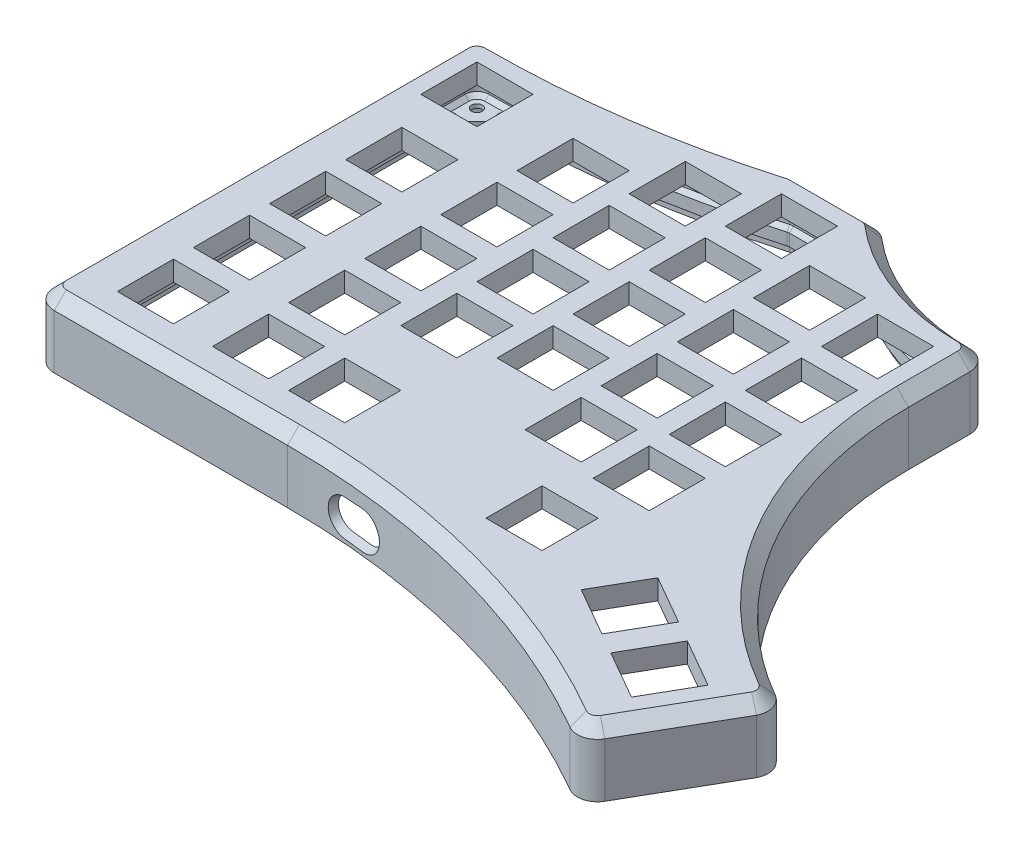
SolidWorks part; units mm, degrees
ref_plane "Front Plane" through (0, 0, 0) normal (0, 0, 1) x (1, 0, 0)
ref_plane "Top Plane" through (0, 0, 0) normal (0, 1, 0) x (1, 0, 0)
ref_plane "Right Plane" through (0, 0, 0) normal (1, 0, 0) x (0, 0, -1)
sketch "Main" plane through (0, 0, 0) normal (0, 1, 0) x (1, 0, 0)
  line L0 (6.4754, 3.5) -> (12.8, 6.5) construction
  line L1 (0, 0) -> (18, 0) construction
  line L2 (0, 0) -> (0, 18) construction
  line L3 (0, 18) -> (18, 18) construction
  line L4 (18, 0) -> (18, 18) construction
  line L5 (2, 16) -> (16, 16)
  line L6 (2, 16) -> (2, 2)
  line L7 (2, 2) -> (16, 2)
  line L8 (16, 16) -> (16, 2)
  line L18 (9, 9) -> (6.4754, 3.5) construction
  line L20 (9, 9) -> (12.8, 6.5) construction
  line L22 (25.4754, 12.5) -> (31.8, 15.5) construction
  line L23 (19, 9) -> (37, 9) construction
  line L24 (19, 9) -> (19, 27) construction
  line L25 (19, 27) -> (37, 27) construction
  line L26 (37, 9) -> (37, 27) construction
  line L27 (21, 25) -> (35, 25)
  line L28 (21, 25) -> (21, 11)
  line L29 (21, 11) -> (35, 11)
  line L30 (35, 25) -> (35, 11)
  line L31 (28, 18) -> (25.4754, 12.5) construction
  line L32 (28, 18) -> (31.8, 15.5) construction
  line L33 (44.4754, 17.5) -> (50.8, 20.5) construction
  line L34 (38, 14) -> (56, 14) construction
  line L35 (38, 14) -> (38, 32) construction
  line L36 (38, 32) -> (56, 32) construction
  line L37 (56, 14) -> (56, 32) construction
  line L38 (40, 30) -> (54, 30)
  line L39 (40, 30) -> (40, 16)
  line L40 (40, 16) -> (54, 16)
  line L41 (54, 30) -> (54, 16)
  line L42 (47, 23) -> (44.4754, 17.5) construction
  line L43 (47, 23) -> (50.8, 20.5) construction
  line L44 (63.4754, 5.5) -> (69.8, 8.5) construction
  line L45 (57, 2) -> (75, 2) construction
  line L46 (57, 2) -> (57, 20) construction
  line L47 (57, 20) -> (75, 20) construction
  line L48 (75, 2) -> (75, 20) construction
  line L49 (59, 18) -> (73, 18)
  line L50 (59, 18) -> (59, 4)
  line L51 (59, 4) -> (73, 4)
  line L52 (73, 18) -> (73, 4)
  line L53 (66, 11) -> (63.4754, 5.5) construction
  line L54 (66, 11) -> (69.8, 8.5) construction
  line L55 (82.4754, 3.5) -> (88.8, 6.5) construction
  line L56 (76, 0) -> (94, 0) construction
  line L57 (76, 0) -> (76, 18) construction
  line L58 (76, 18) -> (94, 18) construction
  line L59 (94, 0) -> (94, 18) construction
  line L60 (78, 16) -> (92, 16)
  line L61 (78, 16) -> (78, 2)
  line L62 (78, 2) -> (92, 2)
  line L63 (92, 16) -> (92, 2)
  line L64 (85, 9) -> (82.4754, 3.5) construction
  line L65 (85, 9) -> (88.8, 6.5) construction
  line L88 (2, -3) -> (16, -3)
  line L89 (2, -3) -> (2, -17)
  line L90 (2, -17) -> (16, -17)
  line L91 (16, -3) -> (16, -17)
  line L92 (21, 6) -> (35, 6)
  line L93 (21, 6) -> (21, -8)
  line L94 (21, -8) -> (35, -8)
  line L95 (35, 6) -> (35, -8)
  line L96 (40, 11) -> (54, 11)
  line L97 (40, 11) -> (40, -3)
  line L98 (40, -3) -> (54, -3)
  line L99 (54, 11) -> (54, -3)
  line L100 (59, -1) -> (73, -1)
  line L101 (59, -1) -> (59, -15)
  line L102 (59, -15) -> (73, -15)
  line L103 (73, -1) -> (73, -15)
  line L104 (78, -3) -> (92, -3)
  line L105 (78, -3) -> (78, -17)
  line L106 (78, -17) -> (92, -17)
  line L107 (92, -3) -> (92, -17)
  line L116 (6.4754, -15.5) -> (12.8, -12.5) construction
  line L117 (0, -19) -> (18, -19) construction
  line L118 (0, -19) -> (0, -1) construction
  line L119 (0, -1) -> (18, -1) construction
  line L120 (18, -19) -> (18, -1) construction
  line L121 (9, -10) -> (6.4754, -15.5) construction
  line L122 (9, -10) -> (12.8, -12.5) construction
  line L123 (25.4754, -6.5) -> (31.8, -3.5) construction
  line L124 (19, -10) -> (37, -10) construction
  line L125 (19, -10) -> (19, 8) construction
  line L126 (19, 8) -> (37, 8) construction
  line L127 (37, -10) -> (37, 8) construction
  line L128 (28, -1) -> (25.4754, -6.5) construction
  line L129 (28, -1) -> (31.8, -3.5) construction
  line L130 (44.4754, -1.5) -> (50.8, 1.5) construction
  line L131 (38, -5) -> (56, -5) construction
  line L132 (38, -5) -> (38, 13) construction
  line L133 (38, 13) -> (56, 13) construction
  line L134 (56, -5) -> (56, 13) construction
  line L135 (47, 4) -> (44.4754, -1.5) construction
  line L136 (47, 4) -> (50.8, 1.5) construction
  line L137 (63.4754, -13.5) -> (69.8, -10.5) construction
  line L138 (57, -17) -> (75, -17) construction
  line L139 (57, -17) -> (57, 1) construction
  line L140 (57, 1) -> (75, 1) construction
  line L141 (75, -17) -> (75, 1) construction
  line L142 (66, -8) -> (63.4754, -13.5) construction
  line L143 (66, -8) -> (69.8, -10.5) construction
  line L144 (82.4754, -15.5) -> (88.8, -12.5) construction
  line L145 (76, -19) -> (94, -19) construction
  line L146 (76, -19) -> (76, -1) construction
  line L147 (76, -1) -> (94, -1) construction
  line L148 (94, -19) -> (94, -1) construction
  line L149 (85, -10) -> (82.4754, -15.5) construction
  line L150 (85, -10) -> (88.8, -12.5) construction
  line L165 (2, -22) -> (16, -22)
  line L166 (2, -22) -> (2, -36)
  line L167 (2, -36) -> (16, -36)
  line L168 (16, -22) -> (16, -36)
  line L169 (21, -13) -> (35, -13)
  line L170 (21, -13) -> (21, -27)
  line L171 (21, -27) -> (35, -27)
  line L172 (35, -13) -> (35, -27)
  line L173 (40, -8) -> (54, -8)
  line L174 (40, -8) -> (40, -22)
  line L175 (40, -22) -> (54, -22)
  line L176 (54, -8) -> (54, -22)
  line L177 (59, -20) -> (73, -20)
  line L178 (59, -20) -> (59, -34)
  line L179 (59, -34) -> (73, -34)
  line L180 (73, -20) -> (73, -34)
  line L181 (78, -22) -> (92, -22)
  line L182 (78, -22) -> (78, -36)
  line L183 (78, -36) -> (92, -36)
  line L184 (92, -22) -> (92, -36)
  line L193 (6.4754, -34.5) -> (12.8, -31.5) construction
  line L194 (0, -38) -> (18, -38) construction
  line L195 (0, -38) -> (0, -20) construction
  line L196 (0, -20) -> (18, -20) construction
  line L197 (18, -38) -> (18, -20) construction
  line L198 (9, -29) -> (6.4754, -34.5) construction
  line L199 (9, -29) -> (12.8, -31.5) construction
  line L200 (25.4754, -25.5) -> (31.8, -22.5) construction
  line L201 (19, -29) -> (37, -29) construction
  line L202 (19, -29) -> (19, -11) construction
  line L203 (19, -11) -> (37, -11) construction
  line L204 (37, -29) -> (37, -11) construction
  line L205 (28, -20) -> (25.4754, -25.5) construction
  line L206 (28, -20) -> (31.8, -22.5) construction
  line L207 (44.4754, -20.5) -> (50.8, -17.5) construction
  line L208 (38, -24) -> (56, -24) construction
  line L209 (38, -24) -> (38, -6) construction
  line L210 (38, -6) -> (56, -6) construction
  line L211 (56, -24) -> (56, -6) construction
  line L212 (47, -15) -> (44.4754, -20.5) construction
  line L213 (47, -15) -> (50.8, -17.5) construction
  line L214 (63.4754, -32.5) -> (69.8, -29.5) construction
  line L215 (57, -36) -> (75, -36) construction
  line L216 (57, -36) -> (57, -18) construction
  line L217 (57, -18) -> (75, -18) construction
  line L218 (75, -36) -> (75, -18) construction
  line L219 (66, -27) -> (63.4754, -32.5) construction
  line L220 (66, -27) -> (69.8, -29.5) construction
  line L221 (82.4754, -34.5) -> (88.8, -31.5) construction
  line L222 (76, -38) -> (94, -38) construction
  line L223 (76, -38) -> (76, -20) construction
  line L224 (76, -20) -> (94, -20) construction
  line L225 (94, -38) -> (94, -20) construction
  line L226 (85, -29) -> (82.4754, -34.5) construction
  line L227 (85, -29) -> (88.8, -31.5) construction
  line L242 (2, -41) -> (16, -41)
  line L243 (2, -41) -> (2, -55)
  line L244 (2, -55) -> (16, -55)
  line L245 (16, -41) -> (16, -55)
  line L246 (21, -32) -> (35, -32)
  line L247 (21, -32) -> (21, -46)
  line L248 (21, -46) -> (35, -46)
  line L249 (35, -32) -> (35, -46)
  line L250 (40, -27) -> (54, -27)
  line L251 (40, -27) -> (40, -41)
  line L252 (40, -41) -> (54, -41)
  line L253 (54, -27) -> (54, -41)
  line L254 (59, -39) -> (73, -39)
  line L255 (59, -39) -> (59, -53)
  line L256 (59, -53) -> (73, -53)
  line L257 (73, -39) -> (73, -53)
  line L258 (78, -41) -> (92, -41)
  line L259 (78, -41) -> (78, -55)
  line L260 (78, -55) -> (92, -55)
  line L261 (92, -41) -> (92, -55)
  line L270 (6.4754, -53.5) -> (12.8, -50.5) construction
  line L271 (0, -57) -> (18, -57) construction
  line L272 (0, -57) -> (0, -39) construction
  line L273 (0, -39) -> (18, -39) construction
  line L274 (18, -57) -> (18, -39) construction
  line L275 (9, -48) -> (6.4754, -53.5) construction
  line L276 (9, -48) -> (12.8, -50.5) construction
  line L277 (25.4754, -44.5) -> (31.8, -41.5) construction
  line L278 (19, -48) -> (37, -48) construction
  line L279 (19, -48) -> (19, -30) construction
  line L280 (19, -30) -> (37, -30) construction
  line L281 (37, -48) -> (37, -30) construction
  line L282 (28, -39) -> (25.4754, -44.5) construction
  line L283 (28, -39) -> (31.8, -41.5) construction
  line L284 (44.4754, -39.5) -> (50.8, -36.5) construction
  line L285 (38, -43) -> (56, -43) construction
  line L286 (38, -43) -> (38, -25) construction
  line L287 (38, -25) -> (56, -25) construction
  line L288 (56, -43) -> (56, -25) construction
  line L289 (47, -34) -> (44.4754, -39.5) construction
  line L290 (47, -34) -> (50.8, -36.5) construction
  line L291 (63.4754, -51.5) -> (69.8, -48.5) construction
  line L292 (57, -55) -> (75, -55) construction
  line L293 (57, -55) -> (57, -37) construction
  line L294 (57, -37) -> (75, -37) construction
  line L295 (75, -55) -> (75, -37) construction
  line L296 (66, -46) -> (63.4754, -51.5) construction
  line L297 (66, -46) -> (69.8, -48.5) construction
  line L298 (82.4754, -53.5) -> (88.8, -50.5) construction
  line L299 (76, -57) -> (94, -57) construction
  line L300 (76, -57) -> (76, -39) construction
  line L301 (76, -39) -> (94, -39) construction
  line L302 (94, -57) -> (94, -39) construction
  line L303 (85, -48) -> (82.4754, -53.5) construction
  line L304 (85, -48) -> (88.8, -50.5) construction
  line L312 (6.4754, -72.5) -> (12.8, -69.5) construction
  line L313 (0, -76) -> (18, -76) construction
  line L314 (0, -76) -> (0, -58) construction
  line L315 (0, -58) -> (18, -58) construction
  line L316 (18, -76) -> (18, -58) construction
  line L317 (2, -60) -> (16, -60)
  line L318 (2, -60) -> (2, -74)
  line L323 (21, -60) -> (35, -60)
  line L324 (21, -60) -> (21, -74)
  line L325 (21, -74) -> (35, -74)
  line L326 (35, -60) -> (35, -74)
  line L327 (25.4754, -72.5) -> (31.8, -69.5) construction
  line L328 (19, -76) -> (37, -76) construction
  line L329 (19, -76) -> (19, -58) construction
  line L330 (-22.0246, 8) -> (-15.7, 11) construction
  line L331 (-28.5, 4.5) -> (-10.5, 4.5) construction
  line L332 (-28.5, 4.5) -> (-28.5, 22.5) construction
  line L333 (-28.5, 22.5) -> (-10.5, 22.5) construction
  line L334 (-10.5, 4.5) -> (-10.5, 22.5) construction
  line L335 (-26.5, 20.5) -> (-12.5, 20.5)
  line L336 (-26.5, 20.5) -> (-26.5, 6.5)
  line L337 (-26.5, 6.5) -> (-12.5, 6.5)
  line L338 (-12.5, 20.5) -> (-12.5, 6.5)
  line L339 (-19.5, 13.5) -> (-22.0246, 8) construction
  line L340 (-19.5, 13.5) -> (-15.7, 11) construction
  line L341 (-21.75, -41) -> (-7.75, -41)
  line L342 (-21.75, -41) -> (-21.75, -55)
  line L343 (-21.75, -55) -> (-7.75, -55)
  line L344 (-7.75, -41) -> (-7.75, -55)
  line L345 (-17.2746, -53.5) -> (-10.95, -50.5) construction
  line L346 (-28.5, -57) -> (-1, -57) construction
  line L347 (-28.5, -57) -> (-28.5, -39) construction
  line L348 (-28.5, -39) -> (-1, -39) construction
  line L349 (-1, -57) -> (-1, -39) construction
  line L350 (-14.75, -48) -> (-17.2746, -53.5) construction
  line L351 (-14.75, -48) -> (-10.95, -50.5) construction
  line L352 (-21.75, -22) -> (-7.75, -22)
  line L353 (-21.75, -22) -> (-21.75, -36)
  line L354 (2, -74) -> (16, -74)
  line L355 (16, -60) -> (16, -74)
  line L356 (9, -67) -> (6.4754, -72.5) construction
  line L357 (9, -67) -> (12.8, -69.5) construction
  line L358 (-17.2746, -72.5) -> (-10.95, -69.5) construction
  line L359 (-28.5, -76) -> (-1, -76) construction
  line L360 (-28.5, -76) -> (-28.5, -58) construction
  line L361 (-28.5, -58) -> (-1, -58) construction
  line L362 (-1, -76) -> (-1, -58) construction
  line L363 (-21.75, -60) -> (-7.75, -60)
  line L364 (-21.75, -60) -> (-21.75, -74)
  line L365 (-21.75, -74) -> (-7.75, -74)
  line L366 (-7.75, -60) -> (-7.75, -74)
  line L367 (-14.75, -67) -> (-17.2746, -72.5) construction
  line L368 (-14.75, -67) -> (-10.95, -69.5) construction
  line L369 (-21.75, -36) -> (-7.75, -36)
  line L370 (-7.75, -22) -> (-7.75, -36)
  line L371 (-17.2746, -34.5) -> (-10.95, -31.5) construction
  line L372 (-28.5, -38) -> (-1, -38) construction
  line L373 (-28.5, -38) -> (-28.5, -20) construction
  line L374 (-28.5, -20) -> (-1, -20) construction
  line L375 (-1, -38) -> (-1, -20) construction
  line L376 (-14.75, -29) -> (-17.2746, -34.5) construction
  line L377 (-14.75, -29) -> (-10.95, -31.5) construction
  line L378 (-21.75, -3) -> (-7.75, -3)
  line L379 (-21.75, -3) -> (-21.75, -17)
  line L380 (-21.75, -17) -> (-7.75, -17)
  line L381 (-7.75, -3) -> (-7.75, -17)
  line L382 (-17.2746, -15.5) -> (-10.95, -12.5) construction
  line L383 (-28.5, -19) -> (-1, -19) construction
  line L384 (-28.5, -19) -> (-28.5, -1) construction
  line L385 (-28.5, -1) -> (-1, -1) construction
  line L386 (-1, -19) -> (-1, -1) construction
  line L387 (-14.75, -10) -> (-17.2746, -15.5) construction
  line L388 (-14.75, -10) -> (-10.95, -12.5) construction
  line L393 (109.2068, -61.578) -> (124.8116, -70.5498) construction
  line L394 (109.2068, -61.578) -> (95.5, -85.4186) construction
  line L398 (124.8116, -70.5498) -> (111.1047, -94.3903) construction
  line L402 (77.7254, -75.5) -> (84.05, -72.5) construction
  line L403 (66.5, -79) -> (94, -79) construction
  line L404 (66.5, -79) -> (66.5, -61) construction
  line L405 (66.5, -61) -> (94, -61) construction
  line L406 (94, -79) -> (94, -61) construction
  line L407 (73.25, -63) -> (87.25, -63)
  line L408 (73.25, -63) -> (73.25, -77)
  line L409 (73.25, -77) -> (87.25, -77)
  line L410 (87.25, -63) -> (87.25, -77)
  line L411 (80.25, -70) -> (77.7254, -75.5) construction
  line L412 (80.25, -70) -> (84.05, -72.5) construction
  line L413 (95.5, -85.4186) -> (111.1047, -94.3903) construction
  line L414 (95.5, -85.4186) -> (124.8116, -70.5498) construction
  line L415 (80.25, -130) -> (110.1558, -77.9842) construction
  line L416 (107.5763, -68.4267) -> (119.7133, -75.4047)
  line L417 (107.5763, -68.4267) -> (100.5983, -80.5637)
  line L418 (119.7133, -75.4047) -> (112.7353, -87.5417)
  line L419 (100.5983, -80.5637) -> (112.7353, -87.5417)
  line L420 (107.5763, -68.4267) -> (112.7353, -87.5417) construction
  line L421 (105.2258, -81.494) -> (110.1558, -77.9842) construction
  line L422 (110.1558, -77.9842) -> (112.204, -82.0455) construction
  line L423 (112.204, -82.0455) -> (105.2258, -81.494) construction
  line L424 (126.5454, -71.5466) -> (142.1502, -80.5184) construction
  line L425 (126.5454, -71.5466) -> (112.8386, -95.3872) construction
  line L426 (142.1502, -80.5184) -> (128.4433, -104.3589) construction
  line L427 (112.8386, -95.3872) -> (128.4433, -104.3589) construction
  line L428 (112.8386, -95.3872) -> (142.1502, -80.5184) construction
  line L430 (124.9149, -78.3953) -> (137.0519, -85.3733)
  line L431 (124.9149, -78.3953) -> (117.9369, -90.5323)
  line L432 (137.0519, -85.3733) -> (130.0739, -97.5103)
  line L433 (117.9369, -90.5323) -> (130.0739, -97.5103)
  line L434 (124.9149, -78.3953) -> (130.0739, -97.5103) construction
  line L435 (122.5644, -91.4626) -> (127.4944, -87.9528) construction
  line L436 (127.4944, -87.9528) -> (129.5426, -92.0141) construction
  line L437 (129.5426, -92.0141) -> (122.5644, -91.4626) construction
  line L448 (19, -58) -> (37, -58) construction
  line L449 (37, -76) -> (37, -58) construction
  line L450 (28, -67) -> (25.4754, -72.5) construction
  line L451 (28, -67) -> (31.8, -69.5) construction
  circle A0 centre (9, 9) radius 2 construction
  circle A1 centre (6.4754, 3.5) radius 1.5 construction
  circle A2 centre (12.8, 6.5) radius 1.5 construction
  circle A6 centre (28, 18) radius 2 construction
  circle A7 centre (25.4754, 12.5) radius 1.5 construction
  circle A8 centre (31.8, 15.5) radius 1.5 construction
  circle A9 centre (47, 23) radius 2 construction
  circle A10 centre (44.4754, 17.5) radius 1.5 construction
  circle A11 centre (50.8, 20.5) radius 1.5 construction
  circle A12 centre (66, 11) radius 2 construction
  circle A13 centre (63.4754, 5.5) radius 1.5 construction
  circle A14 centre (69.8, 8.5) radius 1.5 construction
  circle A15 centre (85, 9) radius 2 construction
  circle A16 centre (82.4754, 3.5) radius 1.5 construction
  circle A17 centre (88.8, 6.5) radius 1.5 construction
  circle A24 centre (9, -10) radius 2 construction
  circle A25 centre (6.4754, -15.5) radius 1.5 construction
  circle A26 centre (12.8, -12.5) radius 1.5 construction
  circle A27 centre (28, -1) radius 2 construction
  circle A28 centre (25.4754, -6.5) radius 1.5 construction
  circle A29 centre (31.8, -3.5) radius 1.5 construction
  circle A30 centre (47, 4) radius 2 construction
  circle A31 centre (44.4754, -1.5) radius 1.5 construction
  circle A32 centre (50.8, 1.5) radius 1.5 construction
  circle A33 centre (66, -8) radius 2 construction
  circle A34 centre (63.4754, -13.5) radius 1.5 construction
  circle A35 centre (69.8, -10.5) radius 1.5 construction
  circle A36 centre (85, -10) radius 2 construction
  circle A37 centre (82.4754, -15.5) radius 1.5 construction
  circle A38 centre (88.8, -12.5) radius 1.5 construction
  circle A45 centre (9, -29) radius 2 construction
  circle A46 centre (6.4754, -34.5) radius 1.5 construction
  circle A47 centre (12.8, -31.5) radius 1.5 construction
  circle A48 centre (28, -20) radius 2 construction
  circle A49 centre (25.4754, -25.5) radius 1.5 construction
  circle A50 centre (31.8, -22.5) radius 1.5 construction
  circle A51 centre (47, -15) radius 2 construction
  circle A52 centre (44.4754, -20.5) radius 1.5 construction
  circle A53 centre (50.8, -17.5) radius 1.5 construction
  circle A54 centre (66, -27) radius 2 construction
  circle A55 centre (63.4754, -32.5) radius 1.5 construction
  circle A56 centre (69.8, -29.5) radius 1.5 construction
  circle A57 centre (85, -29) radius 2 construction
  circle A58 centre (82.4754, -34.5) radius 1.5 construction
  circle A59 centre (88.8, -31.5) radius 1.5 construction
  circle A63 centre (9, -67) radius 2 construction
  circle A64 centre (6.4754, -72.5) radius 1.5 construction
  circle A65 centre (12.8, -69.5) radius 1.5 construction
  circle A66 centre (9, -48) radius 2 construction
  circle A67 centre (6.4754, -53.5) radius 1.5 construction
  circle A68 centre (12.8, -50.5) radius 1.5 construction
  circle A69 centre (28, -39) radius 2 construction
  circle A70 centre (25.4754, -44.5) radius 1.5 construction
  circle A71 centre (31.8, -41.5) radius 1.5 construction
  circle A72 centre (47, -34) radius 2 construction
  circle A73 centre (44.4754, -39.5) radius 1.5 construction
  circle A74 centre (50.8, -36.5) radius 1.5 construction
  circle A75 centre (66, -46) radius 2 construction
  circle A76 centre (63.4754, -51.5) radius 1.5 construction
  circle A77 centre (69.8, -48.5) radius 1.5 construction
  circle A78 centre (85, -48) radius 2 construction
  circle A79 centre (82.4754, -53.5) radius 1.5 construction
  circle A80 centre (88.8, -50.5) radius 1.5 construction
  circle A81 centre (-14.75, -67) radius 2 construction
  circle A82 centre (-17.2746, -72.5) radius 1.5 construction
  circle A83 centre (-10.95, -69.5) radius 1.5 construction
  circle A84 centre (28, -67) radius 2 construction
  circle A85 centre (25.4754, -72.5) radius 1.5 construction
  circle A86 centre (31.8, -69.5) radius 1.5 construction
  circle A87 centre (-19.5, 13.5) radius 2 construction
  circle A88 centre (-22.0246, 8) radius 1.5 construction
  circle A89 centre (-15.7, 11) radius 1.5 construction
  circle A90 centre (-14.75, -48) radius 2 construction
  circle A91 centre (-17.2746, -53.5) radius 1.5 construction
  circle A92 centre (-10.95, -50.5) radius 1.5 construction
  circle A93 centre (-14.75, -29) radius 2 construction
  circle A94 centre (-17.2746, -34.5) radius 1.5 construction
  circle A95 centre (-10.95, -31.5) radius 1.5 construction
  circle A96 centre (-14.75, -10) radius 2 construction
  circle A97 centre (-17.2746, -15.5) radius 1.5 construction
  circle A98 centre (-10.95, -12.5) radius 1.5 construction
  circle A102 centre (80.25, -70) radius 2 construction
  circle A103 centre (77.7254, -75.5) radius 1.5 construction
  circle A104 centre (84.05, -72.5) radius 1.5 construction
  circle A105 centre (80.25, -130) radius 60 construction
  circle A106 centre (110.1558, -77.9842) radius 2 construction
  circle A107 centre (105.2258, -81.494) radius 1.5 construction
  circle A108 centre (112.204, -82.0455) radius 1.5 construction
  circle A109 centre (127.4944, -87.9528) radius 2 construction
  circle A110 centre (122.5644, -91.4626) radius 1.5 construction
  circle A111 centre (129.5426, -92.0141) radius 1.5 construction
  circle A112 centre (62, -66) radius 1.5 construction
  point P9 (9, 16)
  point P10 (9, 18)
  point P11 (2, 9)
  point P12 (0, 9)
  point P30 (28, 25)
  point P31 (28, 27)
  point P32 (21, 18)
  point P33 (19, 18)
  point P46 (47, 30)
  point P47 (47, 32)
  point P48 (40, 23)
  point P49 (38, 23)
  point P64 (66, 18)
  point P65 (66, 20)
  point P66 (59, 11)
  point P67 (57, 11)
  point P82 (85, 16)
  point P83 (85, 18)
  point P84 (78, 9)
  point P85 (76, 9)
  point P102 (9, -60)
  point P103 (9, -58)
  point P104 (2, -67)
  point P105 (0, -67)
  point P124 (-14.75, -60)
  point P125 (-14.75, -58)
  point P126 (-21.75, -67)
  point P127 (-28.5, -67)
  point P297 (-19.5, 20.5)
  point P298 (-19.5, 22.5)
  point P299 (-26.5, 13.5)
  point P300 (-28.5, 13.5)
  point P423 (103.3024, -89.9045)
  point P444 (80.25, -63)
  point P445 (80.25, -61)
  point P446 (73.25, -70)
  point P447 (66.5, -70)
  dimension "D6" = 4
  dimension "D7" = 3
  dimension "D10" = 1
  dimension "D11" = 12
  dimension "D21" = 9.5
  dimension "D22" = 1.5
  dimension "D26" = 120
  dimension "D28" = 3
  dimension "D1" = 18
  dimension "D2" = 14
  dimension "D3" = 3.2
  dimension "D4" = 4.5
  dimension "D5" = 7
  dimension "D8" = 1
  dimension "D9" = 5
  dimension "D12" = 1
  dimension "D13" = 9
  dimension "D14" = 1
  dimension "D15" = 2
  dimension "D16" = 2
  dimension "D17" = 27.5
  dimension "D18" = 1
  dimension "D20" = 1
  dimension "D24" = 1
  dimension "D25" = 8
  dimension "D27" = 2
  dimension "D29" = 15
  dimension "D30" = 32
  dimension "D19" = 4
  dimension "D23" = 4
sketch "Sketch1" plane through (0, 0, 0) normal (0, 1, 0) x (1, 0, 0)
  line L0 (-33.5, 22.5) -> (-33.5, -78)
  line L1 (-28.5, -83) -> (29.7127, -83)
  line L2 (132.778, -106.8511) -> (146.594, -82.8206)
  line L3 (99, 2.7142) -> (99, 18)
  line L6 (38, 32) -> (56, 32) construction
  line L7 (-28.5, -76) -> (-28.5, -58) construction
  line L8 (144.6447, -76.1796) -> (94, -47.0621) construction
  line L9 (142.1502, -80.5184) -> (128.4433, -104.3589) construction
  line L10 (94, 0) -> (94, 18) construction
  line L11 (94, -57) -> (94, -39) construction
  line L12 (128.4433, -104.3589) -> (125.9512, -108.6936) construction
  line L13 (109.2068, -61.578) -> (124.8116, -70.5498) construction
  line L14 (125.9512, -108.6936) -> (74.3045, -79) construction
  line L15 (66.5, -79) -> (94, -79) construction
  line L17 (95.5, -85.4186) -> (111.1047, -94.3903) construction
  line L20 (94, 23) -> (56, 23) construction
  line L21 (56, 14) -> (56, 32) construction
  line L23 (38, 37) -> (56, 37)
  line L27 (38, 14) -> (38, 32) construction
  line L28 (-28.5, 4.5) -> (-28.5, 22.5) construction
  line L29 (-31.5, 22.5) -> (-31.5, -78) construction
  line L30 (-28.5, -81) -> (29.7127, -81) construction
  line L31 (131.0441, -105.8542) -> (144.8356, -81.8665) construction
  line L32 (97, 2.7142) -> (97, 18) construction
  line L33 (38, 35) -> (56, 35) construction
  line L39 (107.5763, -68.4267) -> (119.7133, -75.4047)
  line L40 (-26.5, 20.5) -> (-12.5, 20.5)
  line L41 (-26.5, 20.5) -> (-26.5, 6.5)
  line L42 (-26.5, 6.5) -> (-12.5, 6.5)
  line L43 (-12.5, 20.5) -> (-12.5, 6.5)
  line L44 (-21.75, -3) -> (-7.75, -3)
  line L45 (-21.75, -3) -> (-21.75, -17)
  line L46 (-21.75, -17) -> (-7.75, -17)
  line L47 (-7.75, -3) -> (-7.75, -17)
  line L48 (-21.75, -22) -> (-7.75, -22)
  line L49 (-21.75, -22) -> (-21.75, -36)
  line L50 (-21.75, -36) -> (-7.75, -36)
  line L51 (-7.75, -22) -> (-7.75, -36)
  line L52 (-21.75, -41) -> (-7.75, -41)
  line L53 (-21.75, -41) -> (-21.75, -55)
  line L54 (-21.75, -55) -> (-7.75, -55)
  line L55 (-7.75, -41) -> (-7.75, -55)
  line L56 (-21.75, -60) -> (-7.75, -60)
  line L57 (-21.75, -60) -> (-21.75, -74)
  line L58 (-21.75, -74) -> (-7.75, -74)
  line L59 (-7.75, -60) -> (-7.75, -74)
  line L60 (2, 16) -> (16, 16)
  line L61 (2, 16) -> (2, 2)
  line L62 (2, 2) -> (16, 2)
  line L63 (16, 16) -> (16, 2)
  line L64 (2, -3) -> (16, -3)
  line L65 (2, -3) -> (2, -17)
  line L66 (2, -17) -> (16, -17)
  line L67 (16, -3) -> (16, -17)
  line L68 (2, -22) -> (16, -22)
  line L69 (2, -22) -> (2, -36)
  line L70 (2, -36) -> (16, -36)
  line L71 (16, -22) -> (16, -36)
  line L72 (2, -41) -> (16, -41)
  line L73 (2, -41) -> (2, -55)
  line L74 (2, -55) -> (16, -55)
  line L75 (16, -41) -> (16, -55)
  line L76 (2, -60) -> (16, -60)
  line L77 (2, -60) -> (2, -74)
  line L78 (2, -74) -> (16, -74)
  line L79 (16, -60) -> (16, -74)
  line L80 (21, -60) -> (35, -60)
  line L81 (21, -60) -> (21, -74)
  line L82 (21, -74) -> (35, -74)
  line L83 (35, -60) -> (35, -74)
  line L84 (21, -32) -> (35, -32)
  line L85 (21, -32) -> (21, -46)
  line L86 (21, -46) -> (35, -46)
  line L87 (35, -32) -> (35, -46)
  line L88 (21, 25) -> (35, 25)
  line L89 (21, 25) -> (21, 11)
  line L90 (21, 11) -> (35, 11)
  line L91 (35, 25) -> (35, 11)
  line L92 (21, 6) -> (35, 6)
  line L93 (21, 6) -> (21, -8)
  line L94 (21, -8) -> (35, -8)
  line L95 (35, 6) -> (35, -8)
  line L96 (21, -13) -> (35, -13)
  line L97 (21, -13) -> (21, -27)
  line L98 (21, -27) -> (35, -27)
  line L99 (35, -13) -> (35, -27)
  line L100 (40, 30) -> (54, 30)
  line L101 (40, 30) -> (40, 16)
  line L102 (40, 16) -> (54, 16)
  line L103 (54, 30) -> (54, 16)
  line L104 (40, 11) -> (54, 11)
  line L105 (40, 11) -> (40, -3)
  line L106 (40, -3) -> (54, -3)
  line L107 (54, 11) -> (54, -3)
  line L108 (40, -8) -> (54, -8)
  line L109 (40, -8) -> (40, -22)
  line L110 (40, -22) -> (54, -22)
  line L111 (54, -8) -> (54, -22)
  line L112 (40, -27) -> (54, -27)
  line L113 (40, -27) -> (40, -41)
  line L114 (40, -41) -> (54, -41)
  line L115 (54, -27) -> (54, -41)
  line L116 (59, 18) -> (73, 18)
  line L117 (59, 18) -> (59, 4)
  line L118 (59, 4) -> (73, 4)
  line L119 (73, 18) -> (73, 4)
  line L120 (78, 16) -> (92, 16)
  line L121 (78, 16) -> (78, 2)
  line L122 (78, 2) -> (92, 2)
  line L123 (92, 16) -> (92, 2)
  line L124 (59, -1) -> (73, -1)
  line L125 (59, -1) -> (59, -15)
  line L126 (59, -15) -> (73, -15)
  line L127 (73, -1) -> (73, -15)
  line L128 (78, -3) -> (92, -3)
  line L129 (78, -3) -> (78, -17)
  line L130 (78, -17) -> (92, -17)
  line L131 (92, -3) -> (92, -17)
  line L132 (59, -20) -> (73, -20)
  line L133 (59, -20) -> (59, -34)
  line L134 (59, -34) -> (73, -34)
  line L135 (73, -20) -> (73, -34)
  line L136 (78, -22) -> (92, -22)
  line L137 (78, -22) -> (78, -36)
  line L138 (78, -36) -> (92, -36)
  line L139 (92, -22) -> (92, -36)
  line L140 (59, -39) -> (73, -39)
  line L141 (59, -39) -> (59, -53)
  line L142 (59, -53) -> (73, -53)
  line L143 (73, -39) -> (73, -53)
  line L144 (78, -41) -> (92, -41)
  line L145 (78, -41) -> (78, -55)
  line L146 (78, -55) -> (92, -55)
  line L147 (92, -41) -> (92, -55)
  line L148 (73.25, -63) -> (87.25, -63)
  line L149 (73.25, -63) -> (73.25, -77)
  line L150 (73.25, -77) -> (87.25, -77)
  line L151 (87.25, -63) -> (87.25, -77)
  line L152 (107.5763, -68.4267) -> (100.5983, -80.5637)
  line L153 (119.7133, -75.4047) -> (112.7353, -87.5417)
  line L154 (100.5983, -80.5637) -> (112.7353, -87.5417)
  line L155 (124.9149, -78.3953) -> (137.0519, -85.3733)
  line L156 (124.9149, -78.3953) -> (117.9369, -90.5323)
  line L157 (137.0519, -85.3733) -> (130.0739, -97.5103)
  line L158 (117.9369, -90.5323) -> (130.0739, -97.5103)
  arc A0 (29.7127, -83) -> (125.9512, -108.6936) centre (29.7127, -276.0835) cw
  arc A4 (94, 23) -> (59.2439, 35.8049) centre (94, 76.5714) cw
  arc A7 (36.6, 36.8) -> (-28.5, 27.5) centre (-28.5, 260) cw
  arc A10 (125.9512, -108.6936) -> (132.778, -106.8511) centre (128.4433, -104.3589) ccw
  arc A11 (-33.5, -78) -> (-28.5, -83) centre (-28.5, -78) ccw
  arc A14 (146.594, -82.8206) -> (144.6447, -76.1796) centre (142.1502, -80.5184) ccw
  arc A15 (144.6447, -76.1796) -> (99, 2.7142) centre (190.0036, 2.7142) cw
  arc A16 (99, 18) -> (94, 23) centre (94, 18) ccw
  arc A17 (-33.5, 22.5) -> (-28.5, 27.5) centre (-28.5, 22.5) cw
  arc A29 (36.6, 36.8) -> (38, 37) centre (38, 32) cw
  arc A30 (56, 37) -> (59.2439, 35.8049) centre (56, 32) cw
  arc A31 (37.16, 34.88) -> (-28.5, 25.5) centre (-28.5, 260) cw construction
  arc A32 (-31.5, 22.5) -> (-28.5, 25.5) centre (-28.5, 22.5) cw construction
  arc A33 (-31.5, -78) -> (-28.5, -81) centre (-28.5, -78) ccw construction
  arc A34 (29.7127, -81) -> (126.9481, -106.9597) centre (29.7127, -276.0835) cw construction
  arc A35 (126.9481, -106.9597) -> (131.0441, -105.8542) centre (128.4433, -104.3589) ccw construction
  arc A36 (144.8356, -81.8665) -> (143.6478, -77.9134) centre (142.1502, -80.5184) ccw construction
  arc A37 (143.6478, -77.9134) -> (97, 2.7142) centre (190.0036, 2.7142) cw construction
  arc A38 (97, 18) -> (94, 21) centre (94, 18) ccw construction
  arc A39 (94, 21) -> (57.9463, 34.2829) centre (94, 76.5714) cw construction
  arc A40 (56, 35) -> (57.9463, 34.2829) centre (56, 32) cw construction
  arc A41 (37.16, 34.88) -> (38, 35) centre (38, 32) cw construction
  dimension "D1" = 4
  dimension "D2" = 5
  dimension "D7" = 5.0048
  dimension "D8" = 5
  dimension "D3" = 5
  dimension "D4" = 5
  dimension "D5" = 5
  dimension "D6" = 5
  dimension "D9" = 2
extrude "Main_plate" add sketch "Sketch1" against normal blind 5
chamfer "Main_plate_chamfer" distance 3 16 edges at (146.9524, 0, 79.1088) (111.2334, 0, 42.859) (99, 0, -10.3571) (97.5355, 0, -21.5355) (75.4801, 0, -26.303) (4.3805, 0, -29.8367) (-32.0355, 0, -26.0355) (139.686, 0, 94.8358) (-33.5, 0, 27.75) (129.7462, 0, 109.1862) (-32.0355, 0, 81.5355) (79.5173, 0, 89.534) (0.6063, 0, 83) (57.7285, 0, -36.6917) (47, 0, -37) (37.2929, 0, -36.9497)
sketch "Sketch3" plane through (0, -5, 0) normal (0, -1, 0) x (1, 0, 0)
  line L0 (-28.5, 83) -> (29.7127, 83)
  line L1 (132.778, 106.8511) -> (146.594, 82.8206)
  line L2 (-33.5, 78) -> (-33.5, -22.5)
  line L3 (99, -18) -> (99, -2.7142)
  line L8 (38, -37) -> (56, -37)
  line L9 (-28.5, 81) -> (29.7127, 81)
  line L10 (131.0441, 105.8542) -> (144.8356, 81.8665)
  line L11 (97, -18) -> (97, -2.7142)
  line L12 (38, -35) -> (56, -35)
  line L13 (-31.5, 78) -> (-31.5, -22.5)
  arc A0 (29.7127, 83) -> (125.9512, 108.6936) centre (29.7127, 276.0835) ccw
  arc A1 (125.9512, 108.6936) -> (132.778, 106.8511) centre (128.4433, 104.3589) cw
  arc A2 (-28.5, 83) -> (-33.5, 78) centre (-28.5, 78) ccw
  arc A3 (-33.5, -22.5) -> (-28.5, -27.5) centre (-28.5, -22.5) ccw
  arc A8 (94, -23) -> (99, -18) centre (94, -18) ccw
  arc A10 (144.6447, 76.1796) -> (146.594, 82.8206) centre (142.1502, 80.5184) ccw
  arc A11 (144.6447, 76.1796) -> (99, -2.7142) centre (190.0036, -2.7142) ccw
  arc A23 (94, -23) -> (99, -18) centre (94, -18) ccw construction
  arc A24 (-28.5, -27.5) -> (36.6, -36.8) centre (-28.5, -260) cw
  arc A25 (36.6, -36.8) -> (38, -37) centre (38, -32) ccw
  arc A26 (94, -23) -> (59.2439, -35.8049) centre (94, -76.5714) ccw
  arc A27 (59.2439, -35.8049) -> (56, -37) centre (56, -32) cw
  arc A28 (29.7127, 81) -> (126.9481, 106.9597) centre (29.7127, 276.0835) ccw
  arc A29 (126.9481, 106.9597) -> (131.0441, 105.8542) centre (128.4433, 104.3589) cw
  arc A30 (143.6478, 77.9134) -> (144.8356, 81.8665) centre (142.1502, 80.5184) ccw
  arc A31 (143.6478, 77.9134) -> (97, -2.7142) centre (190.0036, -2.7142) ccw
  arc A32 (94, -21) -> (97, -18) centre (94, -18) ccw
  arc A33 (94, -21) -> (57.9463, -34.2829) centre (94, -76.5714) ccw
  arc A34 (57.9463, -34.2829) -> (56, -35) centre (56, -32) cw
  arc A35 (37.16, -34.88) -> (38, -35) centre (38, -32) ccw
  arc A36 (-28.5, -25.5) -> (37.16, -34.88) centre (-28.5, -260) cw
  arc A37 (-31.5, -22.5) -> (-28.5, -25.5) centre (-28.5, -22.5) ccw
  arc A38 (-28.5, 81) -> (-31.5, 78) centre (-28.5, 78) ccw
  dimension "D1" = 2
extrude "Wall" add sketch "Sketch3" along normal blind 11.5
sketch "Sketch4" plane through (0, -5, 0) normal (0, -1, 0) x (1, 0, 0)
  line L0 (54.62, 75.25) -> (54.62, 44.77) construction
  line L2 (56.12, 75.25) -> (56.12, 44.77)
  line L12 (53.12, 75.25) -> (53.12, 44.77)
  line L16 (39.38, 44.77) -> (39.38, 75.25) construction
  line L17 (37.88, 44.77) -> (37.88, 75.25)
  line L18 (40.88, 44.77) -> (40.88, 75.25)
  arc A9 (56.12, 75.25) -> (53.12, 75.25) centre (54.62, 75.25) ccw
  arc A10 (53.12, 44.77) -> (56.12, 44.77) centre (54.62, 44.77) ccw
  arc A11 (37.88, 44.77) -> (40.88, 44.77) centre (39.38, 44.77) ccw
  arc A12 (40.88, 75.25) -> (37.88, 75.25) centre (39.38, 75.25) ccw
  point P2 (54.62, 60.01)
  point P7 (39.38, 60.01)
  dimension "D1" = 3
extrude "Nice-nano_extrude" cut sketch "Sketch4" against normal blind 2
ref_plane "Plane1" through (0, -14.5, 0) normal (0, -1, 0) x (-1, 0, 0)
sketch "Sketch8" plane through (0, -14.5, 0) normal (0, -1, 0) x (-1, 0, 0)
  line L0 (-39.38, -80.2385) -> (-39.38, -81.2397)
  line L2 (-54.62, -81.5883) -> (-54.62, -82.5966)
  line L51 (-29.7127, -80) -> (28.5, -80)
  line L52 (30.5, -78) -> (30.5, 22.5)
  line L53 (-38, 34) -> (-56, 34)
  line L54 (-96, 18) -> (-96, 2.7142)
  line L55 (-143.9531, -81.395) -> (-130.1772, -105.3558)
  line L56 (-144.8356, -81.8665) -> (-131.0441, -105.8542)
  line L57 (-97, 18) -> (-97, 2.7142)
  line L58 (-38, 35) -> (-56, 35)
  line L59 (31.5, -78) -> (31.5, 22.5)
  line L60 (-29.7127, -81) -> (28.5, -81)
  line L61 (-144.8356, -81.8665) -> (-131.0441, -105.8542)
  line L62 (-97, 18) -> (-97, 2.7142)
  line L63 (-38, 35) -> (-56, 35)
  line L64 (31.5, -78) -> (31.5, 22.5)
  line L65 (-29.7127, -81) -> (28.5, -81)
  arc A0 (-54.62, -81.5883) -> (-127.4465, -106.0928) centre (-29.7127, -276.0835) ccw
  arc A1 (-29.7127, -80) -> (-127.4465, -106.0928) centre (-29.7127, -276.0835) ccw construction
  arc A2 (-54.62, -82.5966) -> (-126.9481, -106.9597) centre (-29.7127, -276.0835) ccw
  arc A3 (-29.7127, -81) -> (-126.9481, -106.9597) centre (-29.7127, -276.0835) ccw construction
  arc A4 (-40.88, -75.25) -> (-37.88, -75.25) centre (-39.38, -75.25) ccw construction
  arc A5 (-56.12, -75.25) -> (-53.12, -75.25) centre (-54.62, -75.25) ccw construction
  arc A91 (28.5, -80) -> (30.5, -78) centre (28.5, -78) ccw
  arc A92 (30.5, 22.5) -> (28.5, 24.5) centre (28.5, 22.5) ccw
  arc A93 (-37.44, 33.92) -> (28.5, 24.5) centre (28.5, 260) ccw
  arc A94 (-37.44, 33.92) -> (-38, 34) centre (-38, 32) ccw
  arc A95 (-56, 34) -> (-57.2976, 33.522) centre (-56, 32) ccw
  arc A96 (-94, 20) -> (-57.2976, 33.522) centre (-94, 76.5714) ccw
  arc A97 (-94, 20) -> (-96, 18) centre (-94, 18) ccw
  arc A98 (-143.1494, -78.7803) -> (-96, 2.7142) centre (-190.0036, 2.7142) ccw
  arc A99 (-143.1494, -78.7803) -> (-143.9531, -81.395) centre (-142.1502, -80.5184) ccw
  arc A100 (-130.1772, -105.3558) -> (-127.4465, -106.0928) centre (-128.4433, -104.3589) ccw
  arc A101 (-29.7127, -80) -> (-39.38, -80.2385) centre (-29.7127, -276.0835) ccw
  arc A102 (-29.7127, -81) -> (-126.9481, -106.9597) centre (-29.7127, -276.0835) ccw
  arc A103 (-131.0441, -105.8542) -> (-126.9481, -106.9597) centre (-128.4433, -104.3589) ccw
  arc A104 (-143.6478, -77.9134) -> (-144.8356, -81.8665) centre (-142.1502, -80.5184) ccw
  arc A105 (-143.6478, -77.9134) -> (-97, 2.7142) centre (-190.0036, 2.7142) ccw
  arc A106 (-94, 21) -> (-97, 18) centre (-94, 18) ccw
  arc A107 (-94, 21) -> (-57.9463, 34.2829) centre (-94, 76.5714) ccw
  arc A108 (-56, 35) -> (-57.9463, 34.2829) centre (-56, 32) ccw
  arc A109 (-37.16, 34.88) -> (-38, 35) centre (-38, 32) ccw
  arc A110 (-37.16, 34.88) -> (28.5, 25.5) centre (28.5, 260) ccw
  arc A111 (31.5, 22.5) -> (28.5, 25.5) centre (28.5, 22.5) ccw
  arc A112 (28.5, -81) -> (31.5, -78) centre (28.5, -78) ccw
  arc A113 (-29.7127, -81) -> (-39.38, -81.2397) centre (-29.7127, -276.0835) ccw
  arc A114 (-131.0441, -105.8542) -> (-126.9481, -106.9597) centre (-128.4433, -104.3589) ccw
  arc A115 (-143.6478, -77.9134) -> (-144.8356, -81.8665) centre (-142.1502, -80.5184) ccw
  arc A116 (-143.6478, -77.9134) -> (-97, 2.7142) centre (-190.0036, 2.7142) ccw
  arc A117 (-94, 21) -> (-97, 18) centre (-94, 18) ccw
  arc A118 (-94, 21) -> (-57.9463, 34.2829) centre (-94, 76.5714) ccw
  arc A119 (-56, 35) -> (-57.9463, 34.2829) centre (-56, 32) ccw
  arc A120 (-37.16, 34.88) -> (-38, 35) centre (-38, 32) ccw
  arc A121 (-37.16, 34.88) -> (28.5, 25.5) centre (28.5, 260) ccw
  arc A122 (31.5, 22.5) -> (28.5, 25.5) centre (28.5, 22.5) ccw
  arc A123 (28.5, -81) -> (31.5, -78) centre (28.5, -78) ccw
  point P29 (-54.62, -76.75)
  point P35 (-39.38, -76.75)
  dimension "D1" = 0
  dimension "D2" = 1
extrude "Side" add sketch "Sketch8" against normal blind 3
chamfer "Side_chamfer" distance 1 angle 45 17 edges at (137.9398, -11.5, 93.8604) (129.2251, -11.5, 107.2553) (34.5478, -11.5, 81.0599) (0.6063, -11.5, 81) (-30.6213, -11.5, 80.1213) (-31.5, -11.5, 27.75) (-30.6213, -11.5, -24.6213) (145.0279, -11.5, 79.6537) (37.5757, -11.5, -34.9698) (109.5023, -11.5, 43.8606) (47, -11.5, -35) (97, -11.5, -10.3571) (57.0371, -11.5, -34.815) (96.1213, -11.5, -20.1213) (74.7887, -11.5, -24.4264) (91.9871, -11.5, 91.2066) (4.6633, -11.5, -27.8568)
sketch "Sketch18" plane through (0, -14.5, 0) normal (0, -1, 0) x (1, 0, 0)
  line L15 (29.7127, 81) -> (-28.5, 81) construction
  line L16 (-31.5, 78) -> (-31.5, -22.5) construction
  line L17 (-26.5, -20.5) -> (-26.5, -6.5) construction
  line L18 (-23.427, 76.2747) -> (-24.6932, 81)
  line L21 (144.8356, 81.8665) -> (131.0441, 105.8542) construction
  line L22 (97, -18) -> (97, -2.7142) construction
  line L23 (-31.5, 78) -> (-31.5, -22.5) construction
  line L27 (-23.427, 76.2747) -> (-24.6524, 80.8476) construction
  line L28 (-25.8771, 79.6229) -> (-28.777, 80.3999) construction
  line L29 (-28.777, 80.3999) -> (-30.8999, 78.277) construction
  line L30 (-30.8999, 78.277) -> (-30.1229, 75.3771) construction
  line L31 (-30.1229, 75.3771) -> (-27.223, 74.6001) construction
  line L32 (-27.223, 74.6001) -> (-25.1001, 76.723) construction
  line L33 (-25.1001, 76.723) -> (-25.8771, 79.6229) construction
  line L34 (-24.6524, 80.8476) -> (-29.2253, 82.073) construction
  line L35 (-29.2253, 82.073) -> (-32.573, 78.7253) construction
  line L36 (-32.573, 78.7253) -> (-31.3476, 74.1524) construction
  line L37 (-31.3476, 74.1524) -> (-26.7747, 72.927) construction
  line L38 (-26.7747, 72.927) -> (-23.427, 76.2747)
  line L39 (-26.7747, 72.927) -> (-31.5, 74.1932)
  line L41 (-31.5, 74.1932) -> (-31.5, 81)
  line L42 (-31.5, 81) -> (-24.6932, 81)
  line L43 (-25.8771, -24.1234) -> (-25.1001, -21.2235) construction
  line L44 (-25.1001, -21.2235) -> (-27.223, -19.1006) construction
  line L45 (-27.223, -19.1006) -> (-30.1229, -19.8776) construction
  line L46 (-30.1229, -19.8776) -> (-30.8999, -22.7776) construction
  line L47 (-30.8999, -22.7776) -> (-28.777, -24.9004) construction
  line L48 (-28.777, -24.9004) -> (-25.8771, -24.1234) construction
  line L49 (-21.75, 60) -> (-21.75, 74) construction
  line L50 (-23.427, -20.7752) -> (-26.7747, -17.4276)
  line L51 (-26.7747, -17.4276) -> (-31.3476, -18.6529) construction
  line L52 (-31.3476, -18.6529) -> (-32.573, -23.2258) construction
  line L53 (-32.573, -23.2258) -> (-29.2253, -26.5735) construction
  line L54 (-29.2253, -26.5735) -> (-24.6524, -25.3482) construction
  line L55 (-24.6524, -25.3482) -> (-23.427, -20.7752) construction
  line L56 (-23.427, -20.7752) -> (-24.7013, -25.5308)
  line L57 (-26.7747, -17.4276) -> (-31.5, -18.6937)
  line L58 (-31.5, -18.6937) -> (-31.5, -25.4687)
  line L59 (-31.5, -25.4687) -> (-24.7013, -25.5308)
  line L60 (92, -2) -> (92, -16) construction
  line L61 (96.8476, -14.1545) -> (92.2747, -12.9292) construction
  line L62 (92.2747, -12.9292) -> (88.927, -16.2768)
  line L63 (88.927, -16.2768) -> (90.1524, -20.8498) construction
  line L64 (90.1524, -20.8498) -> (94.7253, -22.0751) construction
  line L65 (94.7253, -22.0751) -> (98.073, -18.7274) construction
  line L66 (98.073, -18.7274) -> (96.8476, -14.1545) construction
  line L67 (95.6229, -15.3792) -> (92.723, -14.6022) construction
  line L68 (92.723, -14.6022) -> (90.6001, -16.7251) construction
  line L69 (90.6001, -16.7251) -> (91.3771, -19.625) construction
  line L70 (91.3771, -19.625) -> (94.277, -20.402) construction
  line L71 (94.277, -20.402) -> (96.3999, -18.2791) construction
  line L72 (96.3999, -18.2791) -> (95.6229, -15.3792) construction
  line L73 (88.927, -16.2768) -> (90.227, -21.1282)
  line L74 (92.2747, -12.9292) -> (97, -14.1953)
  line L75 (97, -18) -> (97, -2.7142) construction
  line L76 (97, -14.1953) -> (97, -20.8724)
  line L77 (97, -20.8724) -> (90.227, -21.1282)
  line L78 (137.0519, 85.3733) -> (124.9149, 78.3953) construction
  line L79 (138.5692, 79.9256) -> (140.6882, 77.7988) construction
  line L80 (140.6882, 77.7988) -> (143.5896, 78.5706) construction
  line L81 (143.5896, 78.5706) -> (144.3718, 81.4691) construction
  line L82 (144.3718, 81.4691) -> (142.2528, 83.5958) construction
  line L83 (142.2528, 83.5958) -> (139.3515, 82.8241) construction
  line L84 (139.3515, 82.8241) -> (138.5692, 79.9256) construction
  line L85 (136.8953, 79.4803) -> (140.2369, 76.1266) construction
  line L86 (140.2369, 76.1266) -> (144.8121, 77.3436) construction
  line L87 (144.8121, 77.3436) -> (146.0457, 81.9144) construction
  line L88 (146.0457, 81.9144) -> (142.7041, 85.2681) construction
  line L89 (142.7041, 85.2681) -> (138.129, 84.051) construction
  line L90 (138.129, 84.051) -> (136.8953, 79.4803)
  line L91 (138.129, 84.051) -> (142.8566, 85.3086)
  line L92 (144.8356, 81.8665) -> (131.0441, 105.8542) construction
  line L93 (136.8953, 79.4803) -> (140.4037, 75.9593)
  line L94 (142.8566, 85.3086) -> (146.21, 79.4759)
  line L95 (146.21, 79.4759) -> (140.4037, 75.9593)
  circle A4 centre (-28, 77.5) radius 3.5 construction
  circle A9 centre (-28, 77.5) radius 2.6 construction
  circle A11 centre (-28, 77.5) radius 4.1 construction
  circle A16 centre (-28, -22.0005) radius 2.6 construction
  circle A17 centre (-28, -22.0005) radius 4.1 construction
  circle A19 centre (93.5, -17.5021) radius 4.1 construction
  circle A21 centre (93.5, -17.5021) radius 2.6 construction
  arc A22 (94, -21) -> (57.9463, -34.2829) centre (94, -76.5714) ccw construction
  circle A27 centre (-28, 77.5) radius 1.35
  circle A28 centre (-28, -22.0005) radius 3.5 construction
  circle A29 centre (93.5, -17.5021) radius 3.5 construction
  circle A30 centre (141.4705, 80.6973) radius 3.5 construction
  arc A31 (143.6478, 77.9134) -> (97, -2.7142) centre (190.0036, -2.7142) ccw construction
  arc A32 (94, -21) -> (57.9463, -34.2829) centre (94, -76.5714) ccw construction
  arc A33 (37.16, -34.88) -> (-28.5, -25.5) centre (-28.5, -260) ccw construction
  circle A34 centre (-28, -22.0005) radius 1.35
  circle A35 centre (93.5, -17.5021) radius 1.35
  circle A36 centre (141.4705, 80.6973) radius 1.35
  circle A44 centre (141.4705, 80.6973) radius 2.6 construction
  circle A45 centre (141.4705, 80.6973) radius 4.1 construction
  arc A46 (143.6478, 77.9134) -> (97, -2.7142) centre (190.0036, -2.7142) ccw construction
  dimension "D1" = 7
  dimension "D2" = 2.7
  dimension "D3" = 1.5
  dimension "D4" = 45
  dimension "D5" = 5.2
  dimension "D6" = 45
  dimension "D7" = 45
  dimension "D8" = 45
extrude "Nuts_plane" add sketch "Sketch18" against normal blind 3
sketch "Sketch19" plane through (0, -14.5, 0) normal (0, -1, 0) x (1, 0, 0)
  line L1 (-25.1001, 76.723) -> (-25.8771, 79.6229)
  line L2 (-25.8771, 79.6229) -> (-28.777, 80.3999)
  line L3 (-28.777, 80.3999) -> (-30.8999, 78.277)
  line L4 (-30.8999, 78.277) -> (-30.1229, 75.3771)
  line L5 (-30.1229, 75.3771) -> (-27.223, 74.6001)
  line L6 (-27.223, 74.6001) -> (-25.1001, 76.723)
  line L7 (-25.1001, -21.2235) -> (-27.223, -19.1006)
  line L8 (-27.223, -19.1006) -> (-30.1229, -19.8776)
  line L9 (-30.1229, -19.8776) -> (-30.8999, -22.7776)
  line L10 (-30.8999, -22.7776) -> (-28.777, -24.9004)
  line L11 (-28.777, -24.9004) -> (-25.8771, -24.1234)
  line L12 (-25.8771, -24.1234) -> (-25.1001, -21.2235)
  line L13 (95.6229, -15.3792) -> (92.723, -14.6022)
  line L14 (92.723, -14.6022) -> (90.6001, -16.7251)
  line L15 (90.6001, -16.7251) -> (91.3771, -19.625)
  line L16 (91.3771, -19.625) -> (94.277, -20.402)
  line L17 (94.277, -20.402) -> (96.3999, -18.2791)
  line L18 (96.3999, -18.2791) -> (95.6229, -15.3792)
  line L19 (144.3718, 81.4691) -> (142.2528, 83.5958)
  line L20 (142.2528, 83.5958) -> (139.3515, 82.8241)
  line L21 (139.3515, 82.8241) -> (138.5692, 79.9256)
  line L22 (138.5692, 79.9256) -> (140.6882, 77.7988)
  line L23 (140.6882, 77.7988) -> (143.5896, 78.5706)
  line L24 (143.5896, 78.5706) -> (144.3718, 81.4691)
  circle A0 centre (-28, 77.5) radius 2.6 construction
  circle A1 centre (-28, -22.0005) radius 2.6 construction
  circle A2 centre (93.5, -17.5021) radius 2.6 construction
  circle A3 centre (141.4705, 80.6973) radius 2.6 construction
  point P1 (144.3718, 81.4691)
extrude "Nuts_hole" cut sketch "Sketch19" against normal blind 2
fillet "Nuts_fillet" radius 1 16 edges at (-30.5, -13, 73.9252) (-26.7747, -13, 72.927) (-23.427, -13, 76.2747) (-24.4252, -13, 80) (141.8561, -13, 85.0425) (138.129, -13, 84.051) (136.8953, -13, 79.4803) (139.6804, -13, 76.6851) (96, -13, -13.9274) (92.2747, -13, -12.9292) (88.927, -13, -16.2768) (89.9633, -13, -20.1442) (-24.4345, -13, -24.5351) (-23.427, -13, -20.7752) (-26.7747, -13, -17.4276) (-30.5, -13, -18.4258)
sketch "Sketch10" plane through (0, 0, 80) normal (0, 0, -1) x (-1, 0, 0)
  line L1 (-29.7127, -5) -> (28.5, -5) construction
  line L2 (28.5, -16.5) -> (28.5, -3) construction
  circle A0 centre (18.5, -8) radius 3
  dimension "D1" = 6
  dimension "D2" = 10
extrude "Magnet01" cut sketch "Sketch10" against normal blind 1.5
ref_plane "Magnet02_plane1" through (-15.6766, 0, 27.2666) normal (-0.4984, 0, 0.8669) x (0.8669, 0, 0.4984)
ref_plane "Magnet02_plane2" through (-14.6797, 0, 25.5328) normal (0.4984, 0, -0.8669) x (-0.8669, 0, -0.4984)
sketch "Sketch11" plane through (-14.6797, 0, 25.5328) normal (-0.4984, 0, 0.8669) x (0.8669, 0, 0.4984)
  line L1 (66.1316, -5) -> (163.367, -5) construction
  line L2 (163.367, -16.5) -> (163.367, -3) construction
  circle A0 centre (153.367, -8) radius 3
  dimension "D1" = 6
  dimension "D2" = 10
extrude "Magnet02" cut sketch "Sketch11" along normal blind 1.5
sketch "Sketch13" plane through (0, -5, 0) normal (0, -1, 0) x (1, 0, 0)
  line L0 (65, 75) -> (69, 75) construction
  line L1 (65, 76.5) -> (69, 76.5)
  line L2 (65, 73.5) -> (69, 73.5)
  line L3 (69, 70) -> (65, 70) construction
  line L4 (69, 68.5) -> (65, 68.5)
  line L5 (69, 71.5) -> (65, 71.5)
  arc A0 (65, 76.5) -> (65, 73.5) centre (65, 75) ccw
  arc A1 (69, 73.5) -> (69, 76.5) centre (69, 75) ccw
  arc A2 (69, 68.5) -> (69, 71.5) centre (69, 70) ccw
  arc A3 (65, 71.5) -> (65, 68.5) centre (65, 70) ccw
  point P4 (67, 75)
  point P13 (67, 70)
  dimension "D1" = 3
sketch "Sketch14" plane through (0, -5, 0) normal (0, -1, 0) x (1, 0, 0)
  line L0 (65, 70) -> (69, 70) construction
  line L1 (40, 41) -> (54, 27) construction
  line L2 (65, 71.5) -> (69, 71.5) construction
  line L3 (59.46, 66.675) -> (64.54, 66.675) construction
  line L4 (59.46, 66.675) -> (59.46, 60.325) construction
  line L5 (59.46, 60.325) -> (64.54, 60.325) construction
  line L6 (64.54, 66.675) -> (64.54, 60.325) construction
  line L7 (59.46, 66.675) -> (64.54, 60.325) construction
  line L8 (59.46, 60.325) -> (64.54, 66.675) construction
  line L9 (66.71, 62.4) -> (69.71, 62.4) construction
  line L10 (66.71, 62.4) -> (66.71, 59.4) construction
  line L11 (66.71, 59.4) -> (69.71, 59.4) construction
  line L12 (69.71, 62.4) -> (69.71, 59.4) construction
  line L13 (66.71, 62.4) -> (69.71, 59.4) construction
  line L14 (66.71, 59.4) -> (69.71, 62.4) construction
  line L15 (66.71, 66.845) -> (69.71, 66.845) construction
  line L16 (66.71, 66.845) -> (66.71, 63.845) construction
  line L17 (66.71, 63.845) -> (69.71, 63.845) construction
  line L18 (69.71, 66.845) -> (69.71, 63.845) construction
  line L19 (66.71, 66.845) -> (69.71, 63.845) construction
  line L20 (66.71, 63.845) -> (69.71, 66.845) construction
  line L21 (65, 68.5) -> (69, 68.5) construction
  line L22 (65, 75) -> (69, 75) construction
  line L23 (65, 76.5) -> (69, 76.5) construction
  line L24 (65, 73.5) -> (69, 73.5) construction
  line L26 (58.71, 77) -> (70, 77)
  line L27 (57.71, 76) -> (57.71, 59.575)
  line L28 (58.71, 58.575) -> (70, 58.575)
  line L29 (71, 76) -> (71, 59.575)
  line L30 (57.71, 77) -> (71, 58.575) construction
  line L31 (57.71, 58.575) -> (71, 77) construction
  circle A0 centre (64.54, 60.325) radius 1.25 construction
  circle A1 centre (59.46, 60.325) radius 1.25 construction
  circle A2 centre (59.46, 66.675) radius 1.25 construction
  circle A3 centre (64.54, 66.675) radius 1.25 construction
  arc A4 (65, 71.5) -> (65, 68.5) centre (65, 70) ccw construction
  arc A5 (69, 68.5) -> (69, 71.5) centre (69, 70) ccw construction
  arc A6 (65, 76.5) -> (65, 73.5) centre (65, 75) ccw construction
  arc A7 (69, 73.5) -> (69, 76.5) centre (69, 75) ccw construction
  arc A8 (57.71, 59.575) -> (58.71, 58.575) centre (58.71, 59.575) ccw
  arc A9 (70, 58.575) -> (71, 59.575) centre (70, 59.575) ccw
  arc A10 (70, 77) -> (71, 76) centre (70, 76) cw
  arc A11 (58.71, 77) -> (57.71, 76) centre (58.71, 76) ccw
  point P0 (62, 63.5)
  point P1 (47, 34)
  point P11 (62, 63.5)
  point P15 (68.21, 60.9)
  point P16 (68.21, 65.345)
  point P27 (58.21, 60.325)
  point P28 (59.46, 59.075)
  point P29 (67, 70)
  point P34 (67, 75)
  point P37 (70.5, 75)
  point P58 (64.355, 67.7875)
  dimension "D5" = 2.5
  dimension "D8" = 4.445
  dimension "D15" = 1
  dimension "D1" = 15
  dimension "D2" = 29.5
  dimension "D3" = 5.08
  dimension "D4" = 6.35
  dimension "D6" = 2.6
  dimension "D7" = 6.21
  dimension "D9" = 3
  dimension "D10" = 3
  dimension "D11" = 0.5
  dimension "D12" = 0.5
  dimension "D13" = 0.5
  dimension "D14" = 0.5
extrude "Pins_extrude" cut sketch "Sketch14" against normal blind 2
sketch "Sketch15" plane through (0, 0, 81) normal (0, 0, -1) x (-1, 0, 0)
  line L0 (-44.6, -11) -> (-49.4, -11) construction
  line L1 (-44.6, -14.25) -> (-49.4, -14.25) construction
  line L2 (-44.6, -7.75) -> (-49.4, -7.75) construction
  line L3 (-29.7127, 0) -> (-127.4465, 0) construction
  line L4 (33.5, -16.5) -> (33.5, -3) construction
  line L5 (-44.6, -14.75) -> (-49.4, -14.75)
  line L6 (-44.6, -7.25) -> (-49.4, -7.25)
  arc A0 (-44.6, -14.25) -> (-44.6, -7.75) centre (-44.6, -11) ccw construction
  arc A1 (-49.4, -7.75) -> (-49.4, -14.25) centre (-49.4, -11) ccw construction
  arc A2 (-49.4, -7.25) -> (-49.4, -14.75) centre (-49.4, -11) ccw
  arc A3 (-44.6, -14.75) -> (-44.6, -7.25) centre (-44.6, -11) ccw
  point P2 (-47, -11)
  dimension "D1" = 4.8
  dimension "D2" = 6.5
  dimension "D3" = 11
  dimension "D4" = 80.5
  dimension "D5" = 0.5
ref_plane "Charge_port_plane" through (0, 0, 86) normal (0, 0, 1) x (1, 0, 0)
sketch "Sketch16" plane through (0, 0, 86) normal (0, 0, 1) x (1, 0, 0)
  line L4 (49.4, -5.75) -> (44.6, -5.75)
  line L5 (44.6, -16.25) -> (49.4, -16.25)
  line L6 (49.4, -5.75) -> (44.6, -5.75)
  line L7 (44.6, -16.25) -> (49.4, -16.25)
  arc A4 (49.4, -16.25) -> (49.4, -5.75) centre (49.4, -11) ccw
  arc A5 (44.6, -5.75) -> (44.6, -16.25) centre (44.6, -11) ccw
  arc A6 (49.4, -16.25) -> (49.4, -5.75) centre (49.4, -11) ccw
  arc A7 (44.6, -5.75) -> (44.6, -16.25) centre (44.6, -11) ccw
  dimension "D1" = 1.5
loft "Charge_port" cut profiles "Sketch15", "Sketch16"
